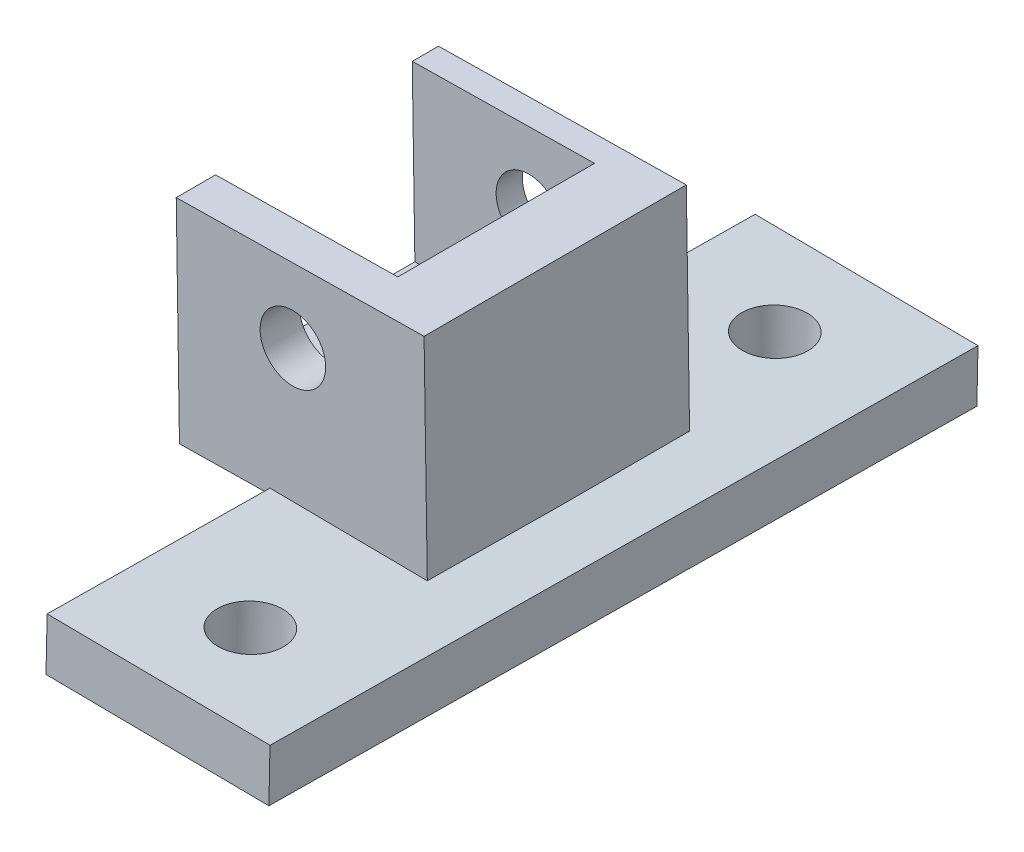
SolidWorks part; units mm, degrees
ref_plane "Front Plane" through (0, 0, 0) normal (0, 0, 1) x (1, 0, 0)
ref_plane "Top Plane" through (0, 0, 0) normal (0, 1, 0) x (1, 0, 0)
ref_plane "Right Plane" through (0, 0, 0) normal (1, 0, 0) x (0, 0, -1)
sketch "Sketch1" plane through (0, 0, 0) normal (0, 0, 1) x (1, 0, 0)
  line L0 (616.5962, 110.6556) -> (616.9091, 90.1601)
  line L1 (604.7125, 110.4741) -> (634.2525, 110.9251) construction
  line L2 (616.9091, 90.1601) -> (640.9147, 90.5267)
  line L3 (640.9147, 90.5267) -> (640.6018, 111.0221)
  line L4 (640.6018, 111.0221) -> (616.5962, 110.6556)
  line L5 (606.4491, 93.8109) -> (629.5989, 94.1643) construction
  line L6 (606.4491, 93.8109) -> (629.5989, 94.1643)
  arc A0 (634.4712, 96.6012) -> (634.2525, 110.9251) centre (627.8931, 103.6644) ccw construction
  arc A1 (629.5989, 94.1643) -> (634.4712, 96.6012) centre (627.8931, 103.6644) ccw construction
  arc A2 (634.4712, 96.6012) -> (634.2525, 110.9251) centre (627.8931, 103.6644) ccw
  arc A3 (629.5989, 94.1643) -> (634.4712, 96.6012) centre (627.8931, 103.6644) ccw
  dimension "D1" = 3.81
  dimension "D2" = 6.35
  dimension "D3" = 24.0084
extrude "Boss-Extrude1" add sketch "Sketch1" against normal blind 21.59 contours A3 L6 L0 L2 L3 L4 A2 region at (623.2298, 93.7486, 0)
sketch "Sketch2" plane through (0, 0, -19.05) normal (0, 0, -1) x (-1, 0, 0)
  line L0 (-616.8509, 93.9697) -> (-616.5962, 110.6556)
  line L1 (-604.6203, 110.4727) -> (-634.2525, 110.9251) construction
  line L2 (-616.5962, 110.6556) -> (-634.2525, 110.9251)
  line L3 (-616.8509, 93.9697) -> (-629.5989, 94.1643) construction
  line L4 (-616.8509, 93.9697) -> (-629.5989, 94.1643)
  arc A0 (-634.2525, 110.9251) -> (-629.5989, 94.1643) centre (-627.8931, 103.6644) ccw construction
  arc A1 (-634.2525, 110.9251) -> (-629.5989, 94.1643) centre (-627.8931, 103.6644) ccw
  circle A2 centre (-627.8931, 103.6644) radius 3.175
  dimension "D1" = 6.35
extrude "Boss-Extrude2" add sketch "Sketch2" along normal up to surface (2.54 mm away) up to face at (630.7326, 98.2176, -21.59)
sketch "Sketch3" plane through (0, 0, 0) normal (0, 0, 1) x (1, 0, 0)
  line L0 (616.5962, 110.6556) -> (640.6018, 111.0221)
  line L1 (640.6018, 111.0221) -> (640.9147, 90.5267)
  line L2 (640.9147, 90.5267) -> (616.9091, 90.1601)
  line L3 (616.9091, 90.1601) -> (640.9147, 90.5267)
  line L4 (616.5962, 110.6556) -> (616.9091, 90.1601)
  circle A0 centre (627.8931, 103.6644) radius 3.175
  arc M1 (634.2525, 110.9251) -> (629.5989, 94.1643) centre (627.8931, 103.6644) cw
  line M2 (629.5989, 94.1643) -> (616.8509, 93.9697)
  line M3 (616.8509, 93.9697) -> (616.9091, 90.1601)
  line M4 (616.9091, 90.1601) -> (640.9147, 90.5267)
  line M5 (640.9147, 90.5267) -> (640.6018, 111.0221)
  line M6 (640.6018, 111.0221) -> (634.2525, 110.9251)
  dimension "D1" = 6.35
extrude "Boss-Extrude3" add sketch "Sketch3" along normal blind 3.81 contours L0 L4 A0 M2 M1 | M6 M1 M2 M3 M4 M5 region at (625.4285, 110.5209, 0) region at (637.432, 110.6552, 0)
ref_plane "Plane1" through (1.0096, 97.2566, -1.0889) normal (0.0104, 0.9999, -0.0112) x (0.9999, -0.0104, 0.0001)
sketch "Sketch6" plane through (1.0096, 97.2566, -1.0889) normal (0.0104, 0.9999, -0.0112) x (0.9999, -0.0104, 0.0001)
  line L1 (624.7011, 42.1668) -> (646.2911, 42.1668)
  line L2 (624.7011, 42.1668) -> (624.7011, -26.4132)
  line L3 (624.7011, -26.4132) -> (646.2911, -26.4132)
  line L4 (646.2911, 42.1668) -> (646.2911, -26.4132)
  circle A0 centre (635.4961, -17.5232) radius 3.175
  circle A1 centre (635.4961, 33.2768) radius 3.175
  dimension "D5" = 8.89
  dimension "D9" = 6.35
  dimension "D10" = 6.35
  dimension "D1" = 21.59
  dimension "D2" = 68.58
  dimension "D3" = 21.59
  dimension "D4" = 6.35
  dimension "D6" = 8.89
  dimension "D7" = 10.795
  dimension "D8" = 10.795
extrude "Boss-Extrude4" add sketch "Sketch6" against normal blind 5.08
